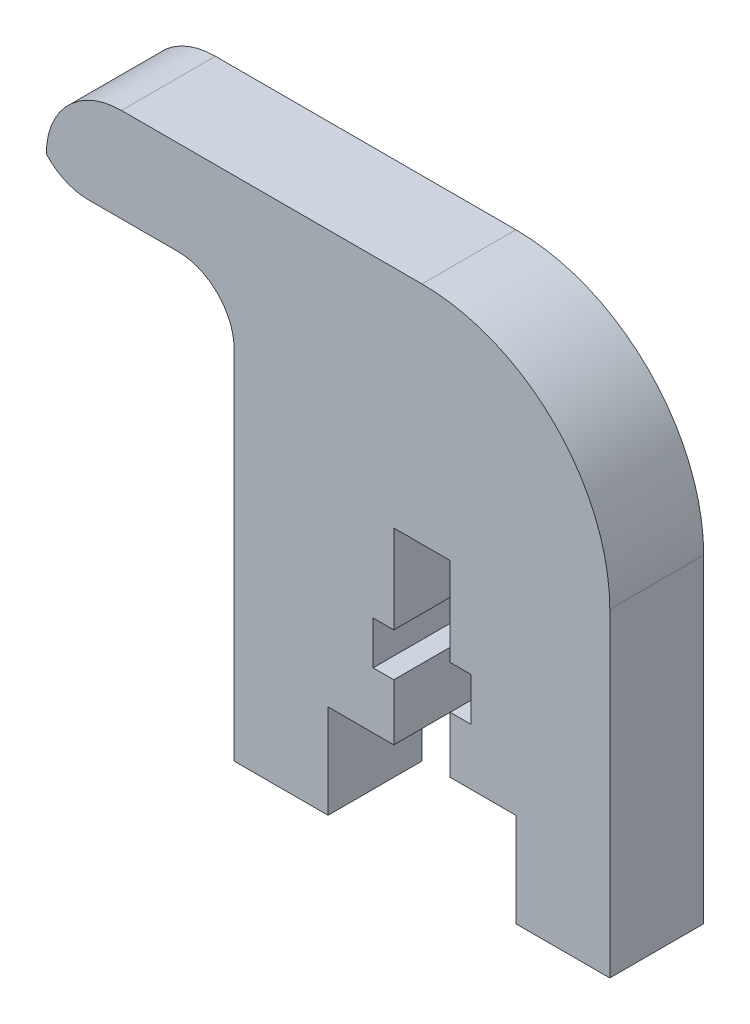
SolidWorks part; units mm, degrees
ref_plane "Front Plane" through (0, 0, 0) normal (0, 0, 1) x (1, 0, 0)
ref_plane "Top Plane" through (0, 0, 0) normal (0, 1, 0) x (1, 0, 0)
ref_plane "Right Plane" through (0, 0, 0) normal (1, 0, 0) x (0, 0, -1)
sketch "Sketch1" plane through (0, 0, 0) normal (0, 0, 1) x (1, 0, 0)
  line L0 (-23.4425, 5) -> (-23.4425, 16.2208) construction
  line L1 (-24.9425, 5) -> (-28.4425, 5)
  line L2 (-28.4425, 0) -> (-33.4425, 0)
  line L3 (-33.4425, 0) -> (-33.4425, 5)
  line L4 (-28.4425, 0) -> (-28.4425, 5)
  line L5 (-21.9425, 5) -> (-18.4425, 5)
  line L6 (-18.4425, 5) -> (-18.4425, 0)
  line L7 (-18.4425, 0) -> (-13.4425, 0)
  line L8 (-13.4425, 0) -> (-13.4425, 5)
  line L9 (-24.9425, 5) -> (-21.9425, 5) construction
  line L10 (-21.9425, 5) -> (-21.9425, 8)
  line L11 (-21.9425, 10.3) -> (-20.8425, 10.3)
  line L12 (-26.0425, 8) -> (-26.0425, 10.3)
  line L13 (-20.8425, 8) -> (-21.9425, 8)
  line L14 (-21.9425, 10.3) -> (-21.9425, 15)
  line L15 (-21.9425, 15) -> (-24.9425, 15)
  line L16 (-24.9425, 15) -> (-24.9425, 10.3)
  line L17 (-24.9425, 8) -> (-26.0425, 8)
  line L18 (-20.8425, 10.3) -> (-20.8425, 8)
  line L19 (-26.0425, 10.3) -> (-24.9425, 10.3)
  line L20 (-24.9425, 8) -> (-24.9425, 5)
  line L21 (-23.4425, 15) -> (-23.4425, 5) construction
  line L22 (-13.4425, 5) -> (-13.4425, 27)
  line L23 (-13.4425, 27) -> (-43.4425, 27)
  line L24 (-43.4425, 27) -> (-43.4425, 22)
  line L25 (-33.4425, 5) -> (-33.4425, 22)
  line L26 (-33.4425, 22) -> (-43.4425, 22)
  dimension "D1" = 10
  dimension "D2" = 5
  dimension "D3" = 5
  dimension "D4" = 5.2
  dimension "D5" = 3
  dimension "D6" = 2.3
  dimension "D7" = 3
  dimension "D8" = 10
  dimension "D9" = 17
  dimension "D10" = 30
  dimension "D11" = 5
extrude "Boss-Extrude1" add sketch "Sketch1" along normal blind 5
fillet "Fillet1" radius 10 1 edges at (-13.4425, 27, 2.5)
fillet "Fillet2" radius 4 1 edges at (-43.4425, 27, 2.5)
fillet "Fillet3" radius 3 2 edges at (-33.4425, 22, 2.5) (-43.4425, 22, 2.5)
